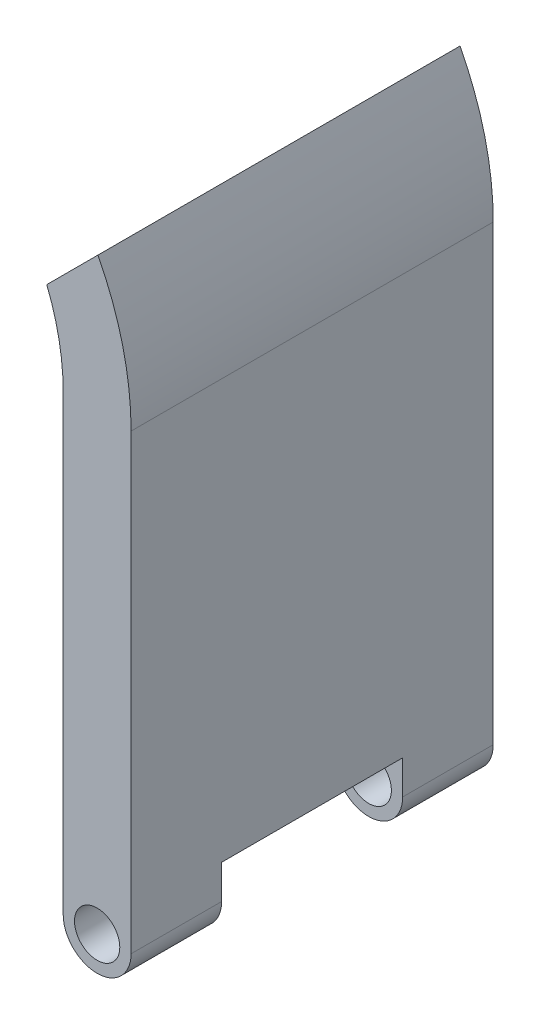
SolidWorks part; units mm, degrees
ref_plane "Front Plane" through (0, 0, 0) normal (0, 0, 1) x (1, 0, 0)
ref_plane "Top Plane" through (0, 0, 0) normal (0, 1, 0) x (1, 0, 0)
ref_plane "Right Plane" through (0, 0, 0) normal (1, 0, 0) x (0, 0, -1)
sketch "Sketch1" plane through (0, 0, 0) normal (0, 0, 1) x (1, 0, 0)
  line L0 (-1.4674, 26) -> (-3.7262, 23.7412)
  line L1 (0, 0) -> (-3, 0)
  line L2 (0, 0) -> (0, 20)
  line L3 (0, 20) -> (-3, 20)
  line L4 (-3, 0) -> (-3, 20)
  arc A0 (0, 20) -> (-1.4674, 26) centre (-13, 20) ccw
  arc A1 (-3, 20) -> (-3.7262, 23.7412) centre (-13, 20) ccw
  circle A2 centre (-1.5, 0) radius 1.5
  circle A3 centre (-1.5, 0) radius 1
  dimension "D3" = 10
  dimension "D4" = 13
  dimension "D7" = 2
  dimension "D1" = 20
  dimension "D2" = 3
  dimension "D5" = 45
  dimension "D6" = 6
extrude "Boss-Extrude1" add sketch "Sketch1" along normal blind 16 contours L4 L1 L2 L3 | A1 L3 A0 L0 | A3 L1 A2 | A3 L1 A2 region at (-1.7566, 22.5251, 0) region at (-1.5, 10.5861, 0) region at (-1.5, -1.4665, 0) region at (-0.25, 0.0335, 0)
ref_plane "Plane1" through (0, 0, 12) normal (0, 0, -1) x (-1, 0, 0)
sketch "Sketch4" plane through (0, 0, 12) normal (0, 0, -1) x (-1, 0, 0)
  line L0 (0, 0) -> (0, 1.5)
  line L1 (0, 1.5) -> (3, 1.5)
  line L2 (3, 1.5) -> (3, 0)
  arc A0 (0, 0) -> (3, 0) centre (1.5, 0) ccw construction
  circle A1 centre (1.5, 0) radius 1 construction
  arc A2 (0, 0) -> (3, 0) centre (1.5, 0) ccw
  circle A3 centre (1.5, 0) radius 1
  arc A4 (3, 0) -> (0, 0) centre (1.5, 0) ccw
  circle A5 centre (1.5, 1.5) radius 0.5
extrude "Cut-Extrude1" cut sketch "Sketch4" along normal blind 8 contours A5 A4 A2 A3 | A5 A4 L2 L1 | A4 A5 | A5 L1 L0 A4 | L1 A5 A4 | L1 A5 | A4 A5 L1 region at (-0.3115, 0.8448, 12) region at (-0.3116, 1.1557, 12) region at (-2.6884, 1.1557, 12) region at (-1.126, 1.4749, 12) region at (-1.5, 1.2735, 12) region at (-1.5, 1.7122, 12) region at (-1.874, 1.4749, 12)
fillet "Fillet1" radius 10 2 edges at (-1, 1.5, 8) (-2, 1.5, 8)
